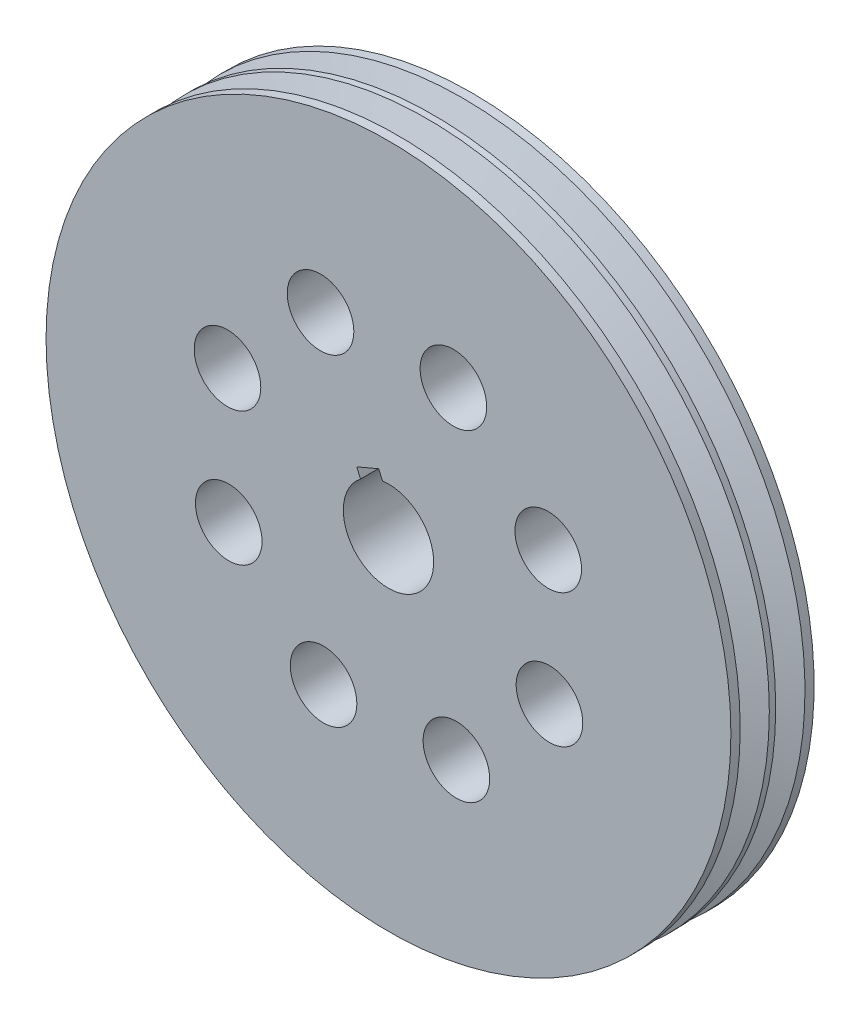
SolidWorks part; units mm, degrees
ref_plane "前视基准面" through (0, 0, 0) normal (0, 0, 1) x (1, 0, 0)
ref_plane "上视基准面" through (0, 0, 0) normal (0, 1, 0) x (1, 0, 0)
ref_plane "右视基准面" through (0, 0, 0) normal (1, 0, 0) x (0, 0, -1)
other "Configuration Table"
sketch "草图2" plane through (0, 0, -367.97) normal (0, 0, 1) x (1, 0, 0)
  circle A0 centre (3169.5278, 918) radius 144
extrude "凸台-拉伸1" add sketch "草图2" against normal up to surface (35 mm away)
sketch "草图3" plane through (0, 0, -367.97) normal (0, 0, 1) x (1, 0, 0)
  line L0 (3165.4017, 940.4781) -> (3156.1994, 936.5645)
  line L1 (3165.4017, 940.4781) -> (3156.1994, 936.5645) construction
  line L2 (3156.1994, 936.5645) -> (3157.7529, 932.9115)
  line L3 (3165.4017, 940.4781) -> (3167.0285, 936.8349)
  arc A0 (3157.7529, 932.9115) -> (3167.0285, 936.8349) centre (3169.5278, 918) ccw
extrude "切除-拉伸1" cut sketch "草图3" against normal through all both and the other way through all
sketch "草图4" plane through (0, 0, -367.97) normal (0, 0, 1) x (1, 0, 0)
  circle A0 centre (3169.5278, 918) radius 43
  circle A1 centre (3169.5278, 918) radius 108
extrude "切除-拉伸2" cut sketch "草图4" against normal up to vertex and the other way through all rebuild error yes
sketch "草图5" plane through (0, 0, -377.3236) normal (0, 0, 1) x (1, 0, 0)
  circle A0 centre (3140.9587, 985.1774) radius 14
  circle A1 centre (3196.828, 985.703) radius 14
  circle A2 centre (3236.7053, 946.5691) radius 14
  circle A3 centre (3237.2309, 890.6998) radius 14
  circle A4 centre (3198.097, 850.8226) radius 14
  circle A5 centre (3142.2276, 850.297) radius 14
  circle A6 centre (3102.3504, 889.4309) radius 14
  circle A7 centre (3101.8248, 945.3002) radius 14
extrude "切除-拉伸3" cut sketch "草图5" against normal through all both and the other way through all
ref_plane "基准面1" through (0, 0, -385.47) normal (0, 0, 1) x (1, 0, 0)
mirror "镜向1" about plane through (0, 0, -385.47) normal (0, 0, 1) rebuild error yes
sketch "草图6" plane through (0, 0, -367.97) normal (0, 0, 1) x (1, 0, 0)
  point P0 (3169.5278, 918)
ref_plane "基准面2" through (0, 918, 0) normal (0, 1, 0) x (1, 0, 0)
sketch "草图7" plane through (0, 918, 0) normal (0, 1, 0) x (1, 0, 0)
  line L0 (3024.5278, 399.47) -> (3041.5278, 393.6164)
  line L1 (3041.5278, 393.6164) -> (3041.5278, 392.3236)
  line L2 (3041.5278, 392.3236) -> (3024.5278, 386.47)
  line L3 (3024.5278, 386.47) -> (3024.5278, 399.47)
  line L4 (3024.5278, 384.47) -> (3041.5278, 378.6164)
  line L5 (3041.5278, 378.6164) -> (3041.5278, 377.3236)
  line L6 (3041.5278, 377.3236) -> (3024.5278, 371.5393)
  line L7 (3024.5278, 371.5393) -> (3024.5278, 384.47)
  line L8 (3025.5278, 402.97) -> (3022.0278, 399.47)
  line L9 (3022.0278, 399.47) -> (3021.3484, 404.3478)
  line L10 (3021.3484, 404.3478) -> (3025.5278, 402.97)
  line L11 (3024.5278, 368.97) -> (3025.8529, 367.6449)
  line L12 (3025.8529, 367.6449) -> (3024.1693, 362.5382)
  line L13 (3024.1693, 362.5382) -> (3017.8026, 366.2984)
  line L14 (3017.8026, 366.2984) -> (3024.5278, 368.97)
  line L15 (3169.5278, 367.97) -> (3169.5278, 431.6996) construction
revolve "切除-旋转1" cut sketch "草图7" angle 360 about L15
